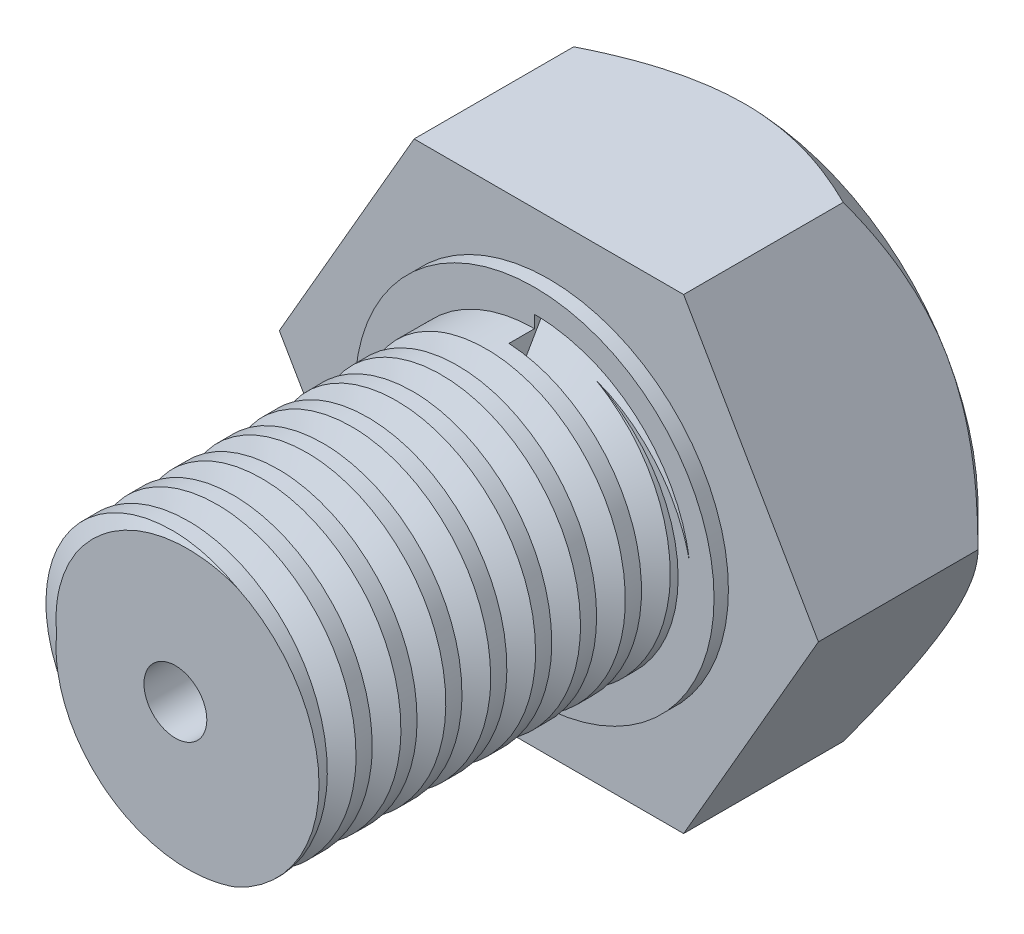
SolidWorks part; units mm, degrees
note: '?' marks a value the reader was unsure of.
ref_plane "Alzado" through (0, 0, 0) normal (0, 0, 1) x (1, 0, 0)
ref_plane "Planta" through (0, 0, 0) normal (0, 1, 0) x (1, 0, 0)
ref_plane "Vista lateral" through (0, 0, 0) normal (1, 0, 0) x (0, 0, -1)
sketch "Croquis9" plane through (0, 0, 0) normal (0, 0, 1) x (1, 0, 0)
  line L0 (-7.5056, 0) -> (-3.7528, -6.5)
  line L1 (7.5056, 0) -> (3.7528, 6.5)
  line L2 (3.7528, 6.5) -> (-3.7528, 6.5)
  line L3 (-3.7528, 6.5) -> (-7.5056, 0)
  line L4 (-3.7528, -6.5) -> (3.7528, -6.5)
  line L5 (3.7528, -6.5) -> (7.5056, 0)
  circle A0 centre (0, 0) radius 6.5 construction
  dimension "D1" = 13
extrude "Saliente-Extruir4" add sketch "Croquis9" along normal blind 5.45
sketch "Croquis10" plane through (0, 0, 5.45) normal (0, 0, 1) x (1, 0, 0)
  circle A0 centre (0, 0) radius 5
  dimension "D1" = 10
extrude "Saliente-Extruir5" add sketch "Croquis10" along normal blind 0.4
sketch "Croquis11" plane through (0, 0, 5.85) normal (0, 0, 1) x (1, 0, 0)
  circle A0 centre (0, 0) radius 4
  dimension "D1" = 8
extrude "Saliente-Extruir6" add sketch "Croquis11" along normal blind 10
ref_axis "Eje2" through (0, 0, 15.85) along (0, 0, -1)?
sketch "Croquis13" plane through (0, 0, 5.85) normal (0, 0, 1) x (1, 0, 0)
  circle A0 centre (0, 0) radius 4 construction
  circle A1 centre (0, 0) radius 4
curve "Hélice/Espiral2" pitch 1.25 height 10 turns 8
ref_plane "Plano1" through (-4, 0, 15.85) normal (0, 0.9988, 0.0497) x (1, 0, 0)
sketch "Croquis16" plane through (0, 0, 0) normal (1, 0, 0) x (0, 0, -1)
  line L0 (-5.85, 4) -> (-15.85, 4) construction
  line L1 (-6.1625, 3.3072) -> (-5.5625, 4.3464)
  line L2 (-5.5625, 4.3464) -> (-6.7625, 4.3464)
  line L3 (-6.7625, 4.3464) -> (-6.1625, 3.3072)
  circle A0 centre (-6.1625, 4) radius 0.3464 construction
  spline S0 degree 3 poles (-5.85, 0) (-5.8759, 0.5202) (-5.9282, 1.5721) (-6.0062, 2.9017) (-6.0844, 3.7918) (-6.1625, 4.1041) (-6.2406, 3.7917) (-6.3187, 2.9021) (-6.3969, 1.5706) (-6.475, 0) (-6.5531, -1.5706) (-6.6312, -2.9021) (-6.7094, -3.7917) (-6.7875, -4.1041) (-6.8656, -3.7917) (-6.9437, -2.9021) (-7.0219, -1.5706) (-7.1, 0) (-7.1781, 1.5706) (-7.2562, 2.9021) (-7.3344, 3.7917) (-7.4125, 4.1041) (-7.4906, 3.7917) (-7.5688, 2.9021) (-7.6469, 1.5706) (-7.725, 0) (-7.8031, -1.5706) (-7.8812, -2.9021) (-7.9594, -3.7917) (-8.0375, -4.1041) (-8.1156, -3.7917) (-8.1937, -2.9021) (-8.2719, -1.5706) (-8.35, 0) (-8.4281, 1.5706) (-8.5063, 2.9021) (-8.5844, 3.7917) (-8.6625, 4.1041) (-8.7406, 3.7917) (-8.8187, 2.9021) (-8.8969, 1.5706) (-8.975, 0) (-9.0531, -1.5706) (-9.1313, -2.9021) (-9.2094, -3.7917) (-9.2875, -4.1041) (-9.3656, -3.7917) (-9.4438, -2.9021) (-9.5219, -1.5706) (-9.6, 0) (-9.6781, 1.5706) (-9.7563, 2.9021) (-9.8344, 3.7917) (-9.9125, 4.1041) (-9.9906, 3.7917) (-10.0688, 2.9021) (-10.1469, 1.5706) (-10.225, 0) (-10.3031, -1.5706) (-10.3813, -2.9021) (-10.4594, -3.7917) (-10.5375, -4.1041) (-10.6156, -3.7917) (-10.6938, -2.9021) (-10.7719, -1.5706) (-10.85, 0) (-10.9281, 1.5706) (-11.0062, 2.9021) (-11.0844, 3.7917) (-11.1625, 4.1041) (-11.2406, 3.7917) (-11.3188, 2.9021) (-11.3969, 1.5706) (-11.475, 0) (-11.5531, -1.5706) (-11.6313, -2.9021) (-11.7094, -3.7917) (-11.7875, -4.1041) (-11.8656, -3.7917) (-11.9437, -2.9021) (-12.0219, -1.5706) (-12.1, 0) (-12.1781, 1.5706) (-12.2563, 2.9021) (-12.3344, 3.7917) (-12.4125, 4.1041) (-12.4906, 3.7917) (-12.5687, 2.9021) (-12.6469, 1.5706) (-12.725, 0) (-12.8031, -1.5706) (-12.8813, -2.9021) (-12.9594, -3.7917) (-13.0375, -4.1041) (-13.1156, -3.7917) (-13.1938, -2.9021) (-13.2719, -1.5706) (-13.35, 0) (-13.4281, 1.5706) (-13.5063, 2.9021) (-13.5844, 3.7917) (-13.6625, 4.1041) (-13.7406, 3.7917) (-13.8188, 2.9021) (-13.8969, 1.5706) (-13.975, 0) (-14.0531, -1.5706) (-14.1313, -2.9021) (-14.2094, -3.7917) (-14.2875, -4.1041) (-14.3656, -3.7917) (-14.4438, -2.9021) (-14.5219, -1.5706) (-14.6, 0) (-14.6781, 1.5706) (-14.7563, 2.9021) (-14.8344, 3.7917) (-14.9125, 4.1041) (-14.9906, 3.7917) (-15.0688, 2.9021) (-15.1469, 1.5706) (-15.225, 0) (-15.3031, -1.5706) (-15.3813, -2.9021) (-15.4594, -3.7917) (-15.5375, -4.1041) (-15.6156, -3.7918) (-15.6938, -2.9017) (-15.7718, -1.5721) (-15.8241, -0.5202) (-15.85, 0) knots 0 0 0 0 0.007812 0.015625 0.023437 0.03125 0.039062 0.046875 0.054687 0.0625 0.070312 0.078125 0.085937 0.09375 0.101562 0.109375 0.117187 0.125 0.132812 0.140625 0.148437 0.15625 0.164062 0.171875 0.179687 0.1875 0.195312 0.203125 0.210937 0.21875 0.226562 0.234375 0.242187 0.25 0.257812 0.265625 0.273437 0.28125 0.289062 0.296875 0.304687 0.3125 0.320312 0.328125 0.335937 0.34375 0.351562 0.359375 0.367187 0.375 0.382812 0.390625 0.398437 0.40625 0.414062 0.421875 0.429687 0.4375 0.445312 0.453125 0.460937 0.46875 0.476562 0.484375 0.492187 0.5 0.507812 0.515625 0.523437 0.53125 0.539062 0.546875 0.554687 0.5625 0.570312 0.578125 0.585937 0.59375 0.601562 0.609375 0.617187 0.625 0.632812 0.640625 0.648437 0.65625 0.664062 0.671875 0.679687 0.6875 0.695312 0.703125 0.710937 0.71875 0.726562 0.734375 0.742187 0.75 0.757812 0.765625 0.773437 0.78125 0.789062 0.796875 0.804687 0.8125 0.820312 0.828125 0.835937 0.84375 0.851562 0.859375 0.867187 0.875 0.882812 0.890625 0.898437 0.90625 0.914062 0.921875 0.929687 0.9375 0.945312 0.953125 0.960937 0.96875 0.976562 0.984375 0.992188 1 1 1 1 construction
  dimension "D1" = 1.2
sweep "Cortar-Barrer5" cut profiles "Croquis16" path "Hélice/Espiral2"
sketch "Croquis19" plane through (0, 0, 0) normal (0, 0, -1) x (-1, 0, 0)
  circle A0 centre (0, 0) radius 6.5
extrude "Cortar-Extruir4" cut sketch "Croquis19" against normal through all draft 45 flip side to cut
sketch "Croquis20" plane through (0, 0, 0) normal (0, 0, -1) x (-1, 0, 0)
  circle A0 centre (0, 0) radius 0.875
  dimension "D1" = 1.75
extrude "Cortar-Extruir5" cut sketch "Croquis20" against normal through all
